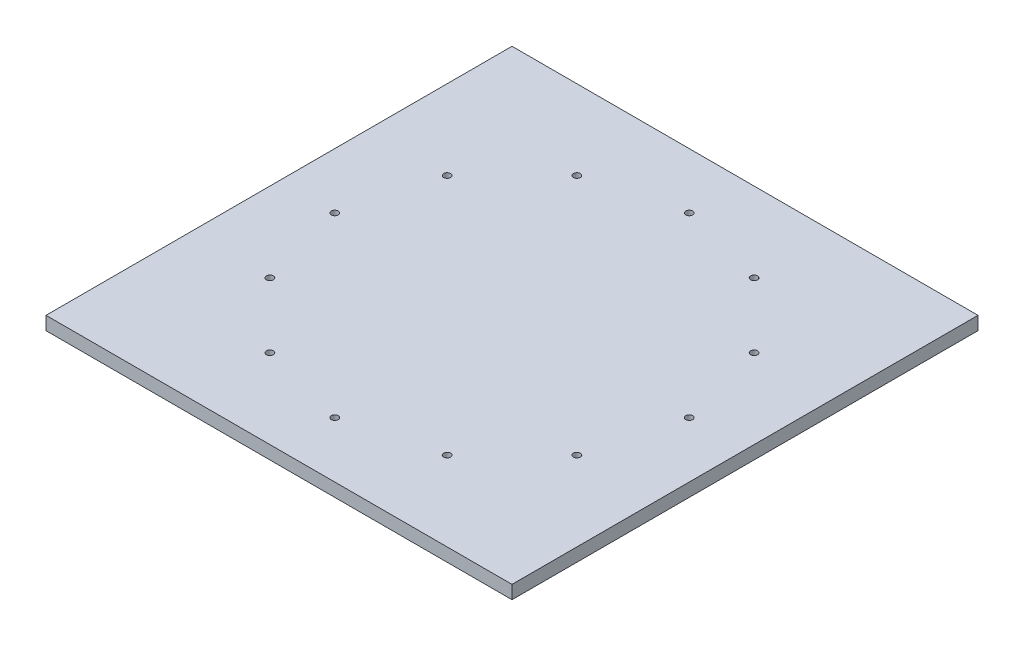
SolidWorks part; units mm, degrees
ref_plane "Front Plane" through (0, 0, 0) normal (0, 0, 1) x (1, 0, 0)
ref_plane "Top Plane" through (0, 0, 0) normal (0, 1, 0) x (1, 0, 0)
ref_plane "Right Plane" through (0, 0, 0) normal (1, 0, 0) x (0, 0, -1)
sketch "Sketch1" plane through (0, 0, 0) normal (0, 1, 0) x (1, 0, 0)
  line L5 (-88.9, 88.9) -> (88.9, 88.9)
  line L6 (-88.9, 88.9) -> (-88.9, -88.9)
  line L7 (-88.9, -88.9) -> (88.9, -88.9)
  line L8 (88.9, 88.9) -> (88.9, -88.9)
  line L9 (-88.9, 88.9) -> (88.9, -88.9) construction
  line L10 (-88.9, -88.9) -> (88.9, 88.9) construction
  circle A0 centre (0, -67.6275) radius 1.3208
  point P0 (0, 0)
  dimension "D3" = 2.6416
  dimension "D1" = 177.8
  dimension "D2" = 177.8
  dimension "D4" = 67.6275
extrude "Boss-Extrude1" add sketch "Sketch1" along normal blind 5.08 contours L8 L5 L6 L7 A0 | A0 region at (0, 0, -0.0117)
sketch "Sketch2" plane through (0, 0, 0) normal (0, 0, 1) x (1, 0, 0)
  line L0 (0, 0) -> (0, 38.8938) construction
pattern_circular "CirPattern1" count 12 over 360 about axis through (0, 0, 0) along (0, 1, 0) reverse direction yes of face at (0, 5.08, 68.9483)
equation "\"Middle Coupler Inner Daimeter\"= 3.875in"
equation "\"Middle Coupler  Wall Thickness\" = 0.25in"
equation "\"Middle Coupler Bottom Thickness\"= 0.2in"
equation "\"Bearing Rail Offset\"= 0.45in"
equation "\"3-56 UNF Tap\"= 0.089in"
equation "\"3-48 Tap\"= 0.079in"
equation "\"3-56 UNF Clearance\"= 0.104in"
equation "\"3-48 Clearance\" = 0.104in"
equation "\"Ball Bearing Distance\"= 0.03in"
equation "\"TCA Outer Diameter\" = 6in"
equation "\"Interstage Aeroframe Wall Thickness\" = 0.072in"
equation "\"Compression Spring OD\"= 0.42in"
equation "\"10-24 Tap\"= 0.157in"
equation "\"10-24 Clearance\"= 0.196in"
equation "\"Lower Stage Fuselage Wall Thickness\" = 0.25in"
equation "\"6-32 Tap\" = 0.107in"
equation "\"6-32 Clearance\" = 0.144"
equation "\"1/4-20 Tap\" = 0.201in"
equation "\"12-24 Tap\" = 0.177in"
equation "\"12-24 Major Diameter\"= 0.216in"
equation "\"D3@Sketch1\"=\"3-48 Clearance\""
equation "\"D4@Sketch1\"=(\"Middle Coupler Inner Daimeter\"+0.625in+0.550in*3/2)/2"
